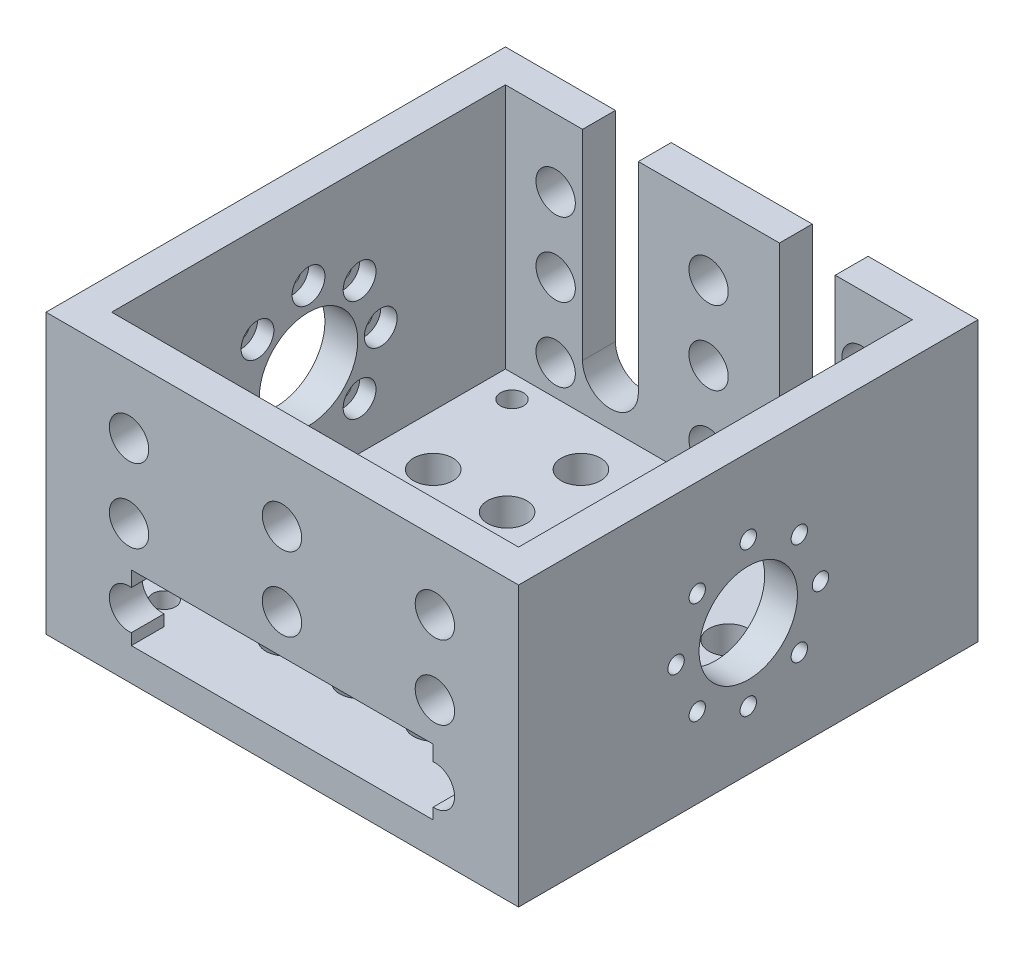
SolidWorks part; units mm, degrees
ref_plane "Front Plane" through (0, 0, 0) normal (0, 0, 1) x (1, 0, 0)
ref_plane "Top Plane" through (0, 0, 0) normal (0, 1, 0) x (1, 0, 0)
ref_plane "Right Plane" through (0, 0, 0) normal (1, 0, 0) x (0, 0, -1)
sketch "Sketch1" plane through (0, 0, 0) normal (0, 0, 1) x (1, 0, 0)
  line L1 (-36, -21.25) -> (36, -21.25)
  line L2 (-36, -21.25) -> (-36, 21.25)
  line L3 (-36, 21.25) -> (36, 21.25)
  line L4 (36, -21.25) -> (36, 21.25)
  line L5 (-36, -21.25) -> (36, 21.25) construction
  line L6 (-36, 21.25) -> (36, -21.25) construction
  point P0 (0, 0)
  dimension "D1" = 42.5
  dimension "D2" = 72
extrude "Boss-Extrude1" add sketch "Sketch1" along normal blind 70
shell "Shell1" thickness 5 removed face at (0, 21.25, 35)
sketch "Sketch3" plane through (36, 0, 0) normal (1, 0, 0) x (0, 0, -1)
  line L0 (-70, -21.25) -> (-70, 21.25) construction
  line L1 (-70, 21.25) -> (0, 21.25) construction
  ellipse E0 centre (-70, 21.25) end of major axis (-10, 21.25) minor radius 40 (-10, 21.25) -> (-70, -18.75) cw
  dimension "D1" = 60
  dimension "D2" = 40
extrude "Cut-Extrude2" [suppressed] cut sketch "Sketch3" against normal through all flip side to cut
sketch "Sketch4" plane through (0, 0, 0) normal (0, 0, -1) x (-1, 0, 0)
  line L1 (31, -16.25) -> (-31, -16.25) construction
  line L2 (23, 3.75) -> (-23, 3.75) construction
  line L3 (0, 0) -> (0, 3.75) construction
  line L4 (-5, -8.75) -> (-5, 21.25)
  line L5 (-36, 21.25) -> (36, 21.25) construction
  line L6 (-5, 21.25) -> (5, 21.25)
  line L7 (5, 21.25) -> (5, -8.75)
  line L8 (0, 3.75) -> (0, -8.75) construction
  circle A0 centre (-23, 3.75) radius 1.5
  circle A1 centre (23, 3.75) radius 1.5
  arc A2 (5, -8.75) -> (-5, -8.75) centre (0, -8.75) cw
  dimension "D1" = 46
  dimension "D4" = 3
  dimension "D2" = 5
  dimension "D3" = 20
  dimension "D5" = 7.5
extrude "Cut-Extrude3" [suppressed] cut sketch "Sketch4" against normal up to next
sketch "Sketch5" plane through (0, 0, 70) normal (0, 0, 1) x (1, 0, 0)
  line L0 (-31, -16.25) -> (31, -16.25) construction
  line L1 (-23, -16.25) -> (23, -16.25)
  line L2 (-23, -16.25) -> (-23, -6.25)
  line L3 (-23, -6.25) -> (23, -6.25)
  line L4 (23, -16.25) -> (23, -6.25)
  line L5 (0, 0) -> (0, -6.25) construction
  dimension "D1" = 10
  dimension "D2" = 46
extrude "Cut-Extrude4" cut sketch "Sketch5" against normal up to next
fillet "Fillet1" [suppressed] radius 2.5
sketch "Sketch6" plane through (36, 0, 0) normal (1, 0, 0) x (0, 0, -1)
  line L1 (-65, -16.25) -> (-5, -16.25) construction
  line L2 (-35, -1.25) -> (-35, 9.75) construction
  line L3 (-35, -1.25) -> (-27.2218, 6.5282) construction
  line L5 (-70, -1.25) -> (0, -1.25) construction
  line L6 (-70, -21.25) -> (-70, 21.25) construction
  line L7 (0, -21.25) -> (0, 21.25) construction
  circle A0 centre (-35, -1.25) radius 7.5
  circle A1 centre (-35, 9.75) radius 1.25
  circle A2 centre (-27.2218, 6.5282) radius 1.25
  circle A3 centre (-24, -1.25) radius 1.25
  circle A4 centre (-27.2218, -9.0282) radius 1.25
  circle A5 centre (-35, -12.25) radius 1.25
  circle A6 centre (-42.7782, -9.0282) radius 1.25
  circle A7 centre (-46, -1.25) radius 1.25
  circle A8 centre (-42.7782, 6.5282) radius 1.25
  point P28 (-35, -1.25)
  dimension "D1" = 11
  dimension "D2" = 2.5
  dimension "D3" = 15
  dimension "D5" = 15
  dimension "D7" = 45
  dimension "D6" = 8
extrude "Cut-Extrude5" cut sketch "Sketch6" against normal up to next
sketch "Sketch8" plane through (31, 0, 0) normal (-1, 0, 0) x (0, 0, 1)
  line L0 (35, -1.25) -> (35, 9.75) construction
  circle A0 centre (35, 9.75) radius 2.5
  circle A1 centre (42.7782, 6.5282) radius 2.5
  circle A2 centre (46, -1.25) radius 2.5
  circle A3 centre (42.7782, -9.0282) radius 2.5
  circle A4 centre (35, -12.25) radius 2.5
  circle A5 centre (27.2218, -9.0282) radius 2.5
  circle A6 centre (24, -1.25) radius 2.5
  circle A7 centre (27.2218, 6.5282) radius 2.5
  circle A13 centre (35, -1.25) radius 7.5 construction
  dimension "D1" = 5
  dimension "D2" = 8
extrude "Cut-Extrude6" cut sketch "Sketch8" against normal blind 2.5
mirror "Mirror1" about plane through (0, 0, 0) normal (1, 0, 0) of "Cut-Extrude6", "Cut-Extrude5"
fillet "Fillet2" [suppressed] radius 2.5
sketch "Sketch11" plane through (0, -21.25, 0) normal (0, -1, 0) x (1, 0, 0)
  line L0 (31, 65) -> (31, 5) construction
  line L1 (-26.5, 8.5) -> (26.5, 8.5) construction
  line L2 (-26.5, 8.5) -> (-26.5, 61.5) construction
  line L3 (-26.5, 61.5) -> (26.5, 61.5) construction
  line L4 (26.5, 8.5) -> (26.5, 61.5) construction
  line L5 (-26.5, 8.5) -> (26.5, 61.5) construction
  line L6 (-26.5, 61.5) -> (26.5, 8.5) construction
  circle A0 centre (-26.5, 61.5) radius 1.75
  circle A1 centre (26.5, 61.5) radius 1.75
  circle A2 centre (26.5, 8.5) radius 1.75
  circle A3 centre (-26.5, 8.5) radius 1.75
  point P0 (0, 35)
  point P13 (31, 35)
  dimension "D1" = 3.5
  dimension "D2" = 53
  dimension "D3" = 53
extrude "Cut-Extrude9" cut sketch "Sketch11" against normal up to next
sketch "Sketch9" plane through (0, -21.25, 0) normal (0, -1, 0) x (1, 0, 0)
  line L0 (0, 5) -> (0, 65) construction
  line L1 (-31, 5) -> (31, 5) construction
  line L2 (23, 65) -> (-23, 65) construction
  line L3 (0, 35) -> (-31, 35) construction
  line L4 (-31, 65) -> (-31, 5) construction
  line L5 (-15.5, 35) -> (-15.5, 5) construction
  line L6 (-15.5, 20) -> (-31, 20) construction
  line L7 (-23.25, 20) -> (-23.25, 5) construction
  circle A0 centre (-23.25, 12.5) radius 3
  dimension "D1" = 6
extrude "Cut-Extrude7" cut sketch "Sketch9" against normal up to next
pattern_linear "LPattern1" count 5 spacing 11.25 along (1, 0, 0) count 5 spacing 11.25 along (0, 0, 1) skipping (0, 4), (4, 0), (4, 4) of "Cut-Extrude7"
sketch "Sketch12" plane through (0, -21.25, 0) normal (0, -1, 0) x (1, 0, 0)
  circle A0 centre (-23.25, 12.5) radius 3
  circle A1 centre (-23.25, 12.5) radius 3 construction
extrude "Boss-Extrude2" add sketch "Sketch12" against normal up to surface (5 mm away) up to face at (21.75, -16.25, 49.25)
sketch "Sketch10" plane through (0, 0, 0) normal (0, 0, -1) x (-1, 0, 0)
  line L0 (0, -16.25) -> (0, 21.25) construction
  line L1 (31, -16.25) -> (-31, -16.25) construction
  line L3 (0, 21.25) -> (0, 2.5) construction
  line L4 (0, 2.5) -> (-31, 2.5) construction
  line L5 (-31, -16.25) -> (-31, 21.25) construction
  line L6 (-31, 2.5) -> (-15.5, 2.5) construction
  line L7 (-15.5, 2.5) -> (-15.5, -16.25) construction
  line L8 (-15.5, -16.25) -> (-15.5, -6.875) construction
  line L9 (-15.5, -6.875) -> (-31, -6.875) construction
  line L10 (-31, -6.875) -> (-23.25, -6.875) construction
  line L11 (-23.25, -6.875) -> (-23.25, -16.25) construction
  circle A0 centre (-23.25, -11.5625) radius 3
  dimension "D1" = 6
  dimension "D2" = 15.5
extrude "Cut-Extrude8" cut sketch "Sketch10" against normal through all
pattern_linear "LPattern2" count 3 spacing 23.3 along (-1, 0, 0) count 3 spacing 11.25 along (0, 1, 0) of "Cut-Extrude8"
sketch "Sketch13" plane through (0, 0, 0) normal (0, 0, -1) x (-1, 0, 0)
  line L0 (0, -16.25) -> (0, -9.25) construction
  line L1 (31, -16.25) -> (-31, -16.25) construction
  line L2 (0, -9.25) -> (-15, -9.25) construction
  line L3 (0, -9.25) -> (15, -9.25) construction
  line L4 (-19.25, -9.25) -> (-19.25, 21.25)
  line L5 (-36, 21.25) -> (36, 21.25) construction
  line L6 (-19.25, 21.25) -> (-10.75, 21.25)
  line L7 (-10.75, 21.25) -> (-10.75, -9.25)
  line L8 (10.75, -9.25) -> (10.75, 21.25)
  line L9 (10.75, 21.25) -> (19.25, 21.25)
  line L10 (19.25, 21.25) -> (19.25, -9.25)
  arc A0 (-10.75, -9.25) -> (-19.25, -9.25) centre (-15, -9.25) cw
  arc A1 (10.75, -9.25) -> (19.25, -9.25) centre (15, -9.25) ccw
  dimension "D1" = 4.25
  dimension "D2" = 15
  dimension "D3" = 7
extrude "Cut-Extrude10" cut sketch "Sketch13" against normal up to next
